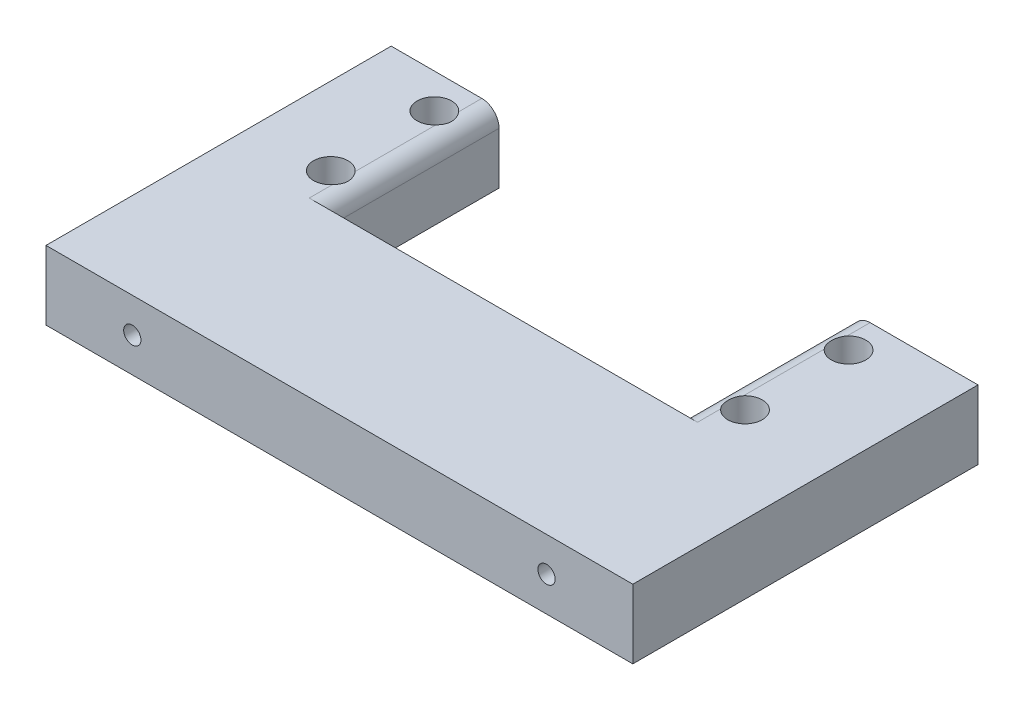
SolidWorks part; units mm, degrees
ref_plane "Front Plane" through (0, 0, 0) normal (0, 0, 1) x (1, 0, 0)
ref_plane "Top Plane" through (0, 0, 0) normal (0, 1, 0) x (1, 0, 0)
ref_plane "Right Plane" through (0, 0, 0) normal (1, 0, 0) x (0, 0, -1)
sketch "Sketch1" plane through (0, 0, 0) normal (0, 1, 0) x (1, 0, 0)
  line L0 (19.0475, 22.279) -> (33.5475, 22.279)
  line L1 (-34.4525, 22.279) -> (-21.9525, 22.279)
  line L2 (-34.4525, 22.279) -> (-34.4525, -17.721)
  line L3 (-34.4525, -17.721) -> (33.5475, -17.721)
  line L4 (33.5475, 22.279) -> (33.5475, -17.721)
  line L5 (-25.4525, 32.7231) -> (-25.4525, -10.4515) construction
  line L6 (-21.9525, 22.279) -> (-21.9525, 2.279)
  line L7 (-21.9525, 2.279) -> (19.0475, 2.279)
  line L8 (19.0475, 22.279) -> (19.0475, 2.279)
  line L9 (22.5475, 35.1405) -> (22.5475, -10.0074) construction
  circle A0 centre (-25.4525, 18.279) radius 2
  circle A1 centre (-25.4525, 6.279) radius 2
  circle A2 centre (22.5475, 18.279) radius 2
  circle A3 centre (22.5475, 6.279) radius 2
  dimension "D8" = 4
  dimension "D9" = 4
  dimension "D12" = 4
  dimension "D13" = 4
  dimension "D1" = 68
  dimension "D2" = 40
  dimension "D3" = 41
  dimension "D4" = 12.5
  dimension "D5" = 20
  dimension "D6" = 3.5
  dimension "D7" = 3.5
  dimension "D10" = 4
  dimension "D11" = 4
extrude "Boss-Extrude1" add sketch "Sketch1" along normal blind 8
sketch "Sketch2" plane through (0, 0, 0) normal (0, 0, 1) x (1, 0, 0)
  line L0 (-34.4525, 8) -> (-34.4525, 0) construction
  line L1 (33.5475, 8) -> (33.5475, 0) construction
  circle A0 centre (-24.4525, 4) radius 1
  circle A1 centre (23.5475, 4) radius 1
  point P6 (-34.4525, 4)
  point P9 (33.5475, 4)
  dimension "D1" = 2
  dimension "D2" = 2
  dimension "D3" = 10
  dimension "D4" = 10
extrude "Cut-Extrude1" cut sketch "Sketch2" against normal blind 8 from surface starting at face at (-0.4525, 4, 17.721)
fillet "Fillet1" radius 2 2 edges at (-21.9525, 8, -12.279) (19.0475, 8, -12.279)
